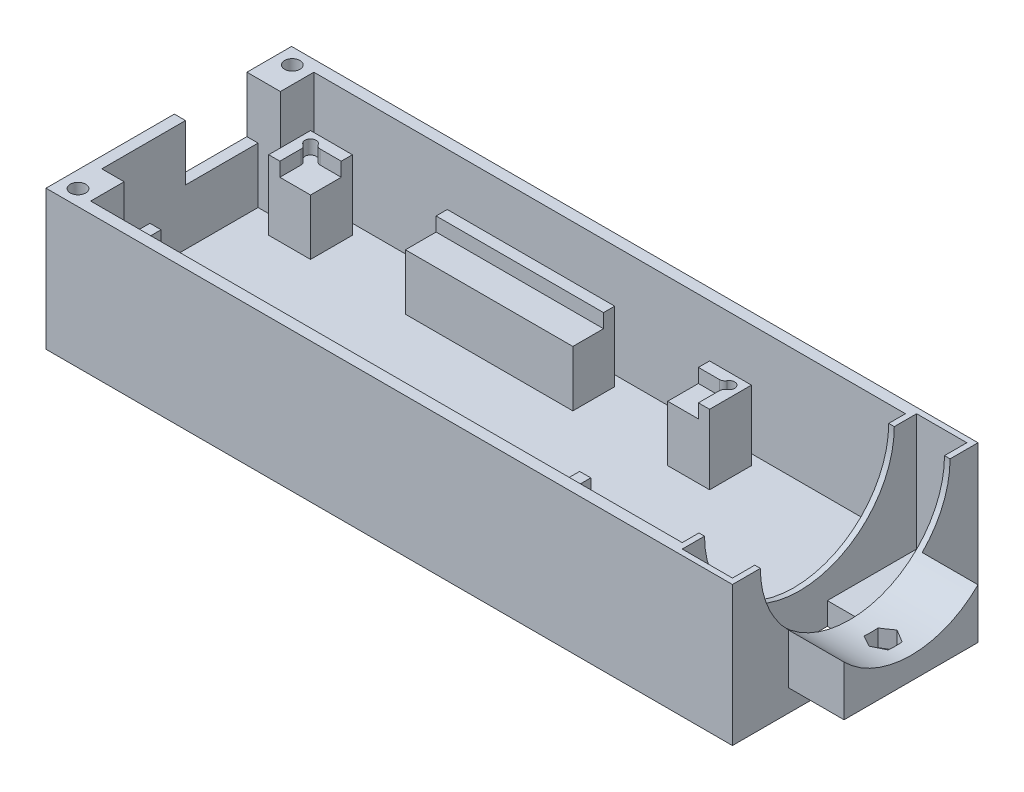
SolidWorks part; units mm, degrees
ref_plane "Front Plane" through (0, 0, 0) normal (0, 0, 1) x (1, 0, 0)
ref_plane "Top Plane" through (0, 0, 0) normal (0, 1, 0) x (1, 0, 0)
ref_plane "Right Plane" through (0, 0, 0) normal (1, 0, 0) x (0, 0, -1)
sketch "Sketch2" plane through (0, 0, 0) normal (0, 1, 0) x (1, 0, 0)
  line L4 (451.485, -2.54) -> (374.015, -2.54)
  line L5 (451.485, -2.54) -> (451.485, 74.93)
  line L6 (451.485, 74.93) -> (374.015, 74.93)
  line L7 (374.015, -2.54) -> (374.015, 74.93)
  line L8 (469.9, -19.685) -> (-50.8, -19.685)
  line L9 (469.9, -19.685) -> (469.9, 92.075)
  line L10 (469.9, 92.075) -> (-50.8, 92.075)
  line L11 (-50.8, -19.685) -> (-50.8, 92.075)
  line L12 (449.58, -0.635) -> (317.5, -0.635)
  line L13 (449.58, -0.635) -> (449.58, 89.789)
  line L14 (449.58, 89.789) -> (317.5, 89.789)
  line L15 (317.5, -0.635) -> (317.5, 89.789)
  line L16 (445.77, 3.175) -> (326.263, 3.175)
  line L17 (445.77, 3.175) -> (445.77, 85.979)
  line L18 (445.77, 85.979) -> (326.263, 85.979)
  line L19 (326.263, 3.175) -> (326.263, 85.979)
  line L20 (326.263, 48.895) -> (313.944, 48.895)
  line L21 (326.263, 48.895) -> (326.263, 77.089)
  line L22 (326.263, 77.089) -> (313.944, 77.089)
  line L23 (313.944, 48.895) -> (313.944, 77.089)
  line L24 (313.944, 68.453) -> (307.34, 68.453)
  line L25 (313.944, 68.453) -> (313.944, 77.089)
  line L26 (313.944, 77.089) -> (307.34, 77.089)
  line L27 (307.34, 68.453) -> (307.34, 77.089)
  line L28 (209.55, 92.075) -> (209.55, -19.685)
  line L33 (209.55, 48.895) -> (184.15, 61.595)
  line L34 (184.15, 61.595) -> (184.15, 10.795)
  line L35 (184.15, 10.795) -> (209.55, 23.495)
  circle A0 centre (412.75, 36.195) radius 20.32
  circle A1 centre (412.75, 36.195) radius 29.21
  point P34 (0, 0)
  dimension "D1" = 40.64
  dimension "D2" = 58.42
  dimension "D3" = 82.804
  dimension "D4" = 90.424
  dimension "D5" = 132.08
  dimension "D6" = 119.507
  dimension "D7" = 3.81
  dimension "D8" = 3.81
  dimension "D9" = 28.194
  dimension "D10" = 8.636
  dimension "D11" = 12.319
  dimension "D12" = 520.7
  dimension "D13" = 33.02
  dimension "D14" = 33.02
  dimension "D15" = 111.76
  dimension "D16" = 77.47
  dimension "D17" = 57.15
  dimension "D18" = 38.735
  dimension "D19" = 77.47
  dimension "D20" = 38.735
  dimension "D21" = 50.8
  dimension "D22" = 8.89
  dimension "D23" = 55.88
  dimension "D24" = 12.7
  dimension "D25" = 25.4
  dimension "D26" = 12.7
  dimension "D27" = 25.4
sketch "Sketch3" plane through (0, 0, 0) normal (0, 1, 0) x (1, 0, 0)
  line L1 (-50.8, 92.075) -> (469.9, 92.075)
  line L2 (-50.8, 92.075) -> (-50.8, -19.685)
  line L3 (-50.8, -19.685) -> (469.9, -19.685)
  line L4 (469.9, 92.075) -> (469.9, -19.685)
extrude "Boss-Extrude1" add sketch "Sketch3" along normal blind 63.5
extrude "Cut-Extrude1" cut sketch "Sketch2" along normal blind 111.76 from offset 6.35 contours L6 L7 L4 L5
sketch "Sketch4" plane through (0, 0, 19.685) normal (0, 0, 1) x (1, 0, 0)
  line L0 (469.9, 0) -> (254, 0)
  line L1 (-50.8, 0) -> (469.9, 0) construction
  line L2 (469.9, 12.7) -> (330.2, 12.7)
  line L4 (469.9, 63.5) -> (469.9, 0) construction
  line L5 (330.2, 12.7) -> (279.4, 63.5)
  line L7 (469.9, 12.7) -> (469.9, 63.5)
  line L8 (279.4, 63.5) -> (469.9, 63.5)
  circle A0 centre (330.2, 63.5) radius 50.8
  line M3 (469.9, 0) -> (469.9, 63.5)
  line M4 (469.9, 63.5) -> (-50.8, 63.5)
  dimension "D1" = 215.9
  dimension "D2" = 139.7
  dimension "D3" = 12.7
  dimension "D4" = 135
  dimension "D5" = 50.8
extrude "Cut-Extrude2" cut sketch "Sketch4" against normal blind 156.718 contours L8 L5 L7 M4 | L5 L2 M3 M4 | L8 A0 L5 M4 | L5 A0 | A0 region at (419.355, 36.5649, 19.685) region at (300.5338, 33.8338, 19.685) region at (336.7868, 43.7396, 19.685) region at (330.2, 85.0602, 19.685)
sketch "Sketch5" plane through (0, 0, 0) normal (1, 0, 0) x (0, 0, -1)
  line L1 (92.075, 63.5) -> (-19.685, 63.5) construction
  circle A0 centre (36.195, 63.5) radius 43.18
  dimension "D1" = 86.36
extrude "Cut-Extrude3" cut sketch "Sketch5" along normal blind 355.6 contours A0
sketch "Sketch6" plane through (0, 63.5, 0) normal (0, 1, 0) x (1, 0, 0)
  line L0 (469.9, -19.685) -> (-50.8, -19.685) construction
  line L1 (-45.72, -14.605) -> (233.68, -14.605)
  line L2 (-45.72, -14.605) -> (-45.72, 86.995)
  line L3 (-45.72, 86.995) -> (233.68, 86.995)
  line L4 (233.68, -14.605) -> (233.68, 86.995)
  line L5 (-50.8, -19.685) -> (-50.8, 92.075) construction
  dimension "D1" = 101.6
  dimension "D2" = 5.08
  dimension "D3" = 5.08
  dimension "D4" = 279.4
extrude "Cut-Extrude4" cut sketch "Sketch6" against normal blind 50.8
sketch "Sketch7" plane through (0, 63.5, 0) normal (0, 1, 0) x (1, 0, 0)
  line L0 (245.1614, -13.805) -> (237.4386, -13.805)
  line L1 (231.3, 36.195) -> (251.3, 36.195)
  line L2 (241.3, 36.195) -> (241.3, -13.805)
  line L3 (-45.72, 36.195) -> (169.3056, 36.195)
  line L4 (-45.72, 86.995) -> (-45.72, -14.605) construction
  arc A0 (237.4386, -13.805) -> (231.3, 36.195) centre (438, 36.195) cw
  arc A1 (245.1614, -13.805) -> (251.3, 36.195) centre (44.6, 36.195) ccw
  dimension "D1" = 287.02
revolve "Cut-Revolve1" cut sketch "Sketch7" angle 360 about L3 region at (243.6576, 63.5, 10.203) region at (245.6519, 63.5, -16.5343)
sketch "Sketch8" plane through (0, 0, 0) normal (0, -1, 0) x (1, 0, 0)
  line L0 (261.62, 19.685) -> (261.62, -5.715)
  line L1 (469.9, 19.685) -> (-50.8, 19.685) construction
  line L2 (469.9, -92.075) -> (-50.8, -92.075) construction
  line L3 (261.62, -66.675) -> (287.02, -66.675)
  line L4 (287.02, -66.675) -> (287.02, -5.715)
  line L5 (287.02, -5.715) -> (261.62, -5.715)
  line L6 (-50.8, 19.685) -> (-50.8, -92.075) construction
  line L7 (261.62, 19.685) -> (609.548, 88.4252)
  line L8 (609.548, 88.4252) -> (609.548, -173.8625)
  line L9 (609.548, -173.8625) -> (261.62, -92.075)
  line L10 (261.62, -66.675) -> (261.62, -92.075)
  dimension "D1" = 312.42
  dimension "D2" = 25.4
  dimension "D3" = 25.4
  dimension "D4" = 25.4
extrude "Cut-Extrude5" cut sketch "Sketch8" against normal blind 174.244 contours L9 L10 L3 L4 L5 L0 L7 L8
sketch "Sketch9" plane through (0, 0, 0) normal (0, -1, 0) x (1, 0, 0)
  line L1 (287.02, -5.715) -> (261.62, -5.715)
  line L2 (287.02, -5.715) -> (287.02, -66.675)
  line L3 (287.02, -66.675) -> (261.62, -66.675)
  line L4 (261.62, -5.715) -> (261.62, -66.675)
extrude "Cut-Extrude6" cut sketch "Sketch9" against normal blind 10.16
sketch "Sketch11" plane through (0, 63.5, 0) normal (0, 1, 0) x (1, 0, 0)
  line L1 (-50.8, 92.075) -> (-35.56, 92.075)
  line L2 (-50.8, 92.075) -> (-50.8, 71.755)
  line L3 (-50.8, 71.755) -> (-35.56, 71.755)
  line L4 (-35.56, 92.075) -> (-35.56, 71.755)
  line L5 (-50.8, -19.685) -> (-35.56, -19.685)
  line L6 (-50.8, -19.685) -> (-50.8, 0.635)
  line L7 (-50.8, 0.635) -> (-35.56, 0.635)
  line L8 (-35.56, -19.685) -> (-35.56, 0.635)
  dimension "D1" = 15.24
  dimension "D2" = 20.32
  dimension "D3" = 20.32
  dimension "D4" = 15.24
extrude "Boss-Extrude2" add sketch "Sketch11" against normal up to next
sketch "Sketch10" plane through (0, 0, 0) normal (0, -1, 0) x (1, 0, 0)
  line L0 (-50.8, -92.075) -> (-50.8, 19.685) construction
  line L1 (261.62, -92.075) -> (-50.8, -92.075) construction
  line L2 (252.3, -92.075) -> (241.3, -92.075)
  line L3 (246.8, -91.3139) -> (252.3, -88.1384)
  line L4 (252.3, -88.1384) -> (252.3, -81.7876)
  line L5 (252.3, -81.7876) -> (246.8, -78.6121)
  line L6 (246.8, -78.6121) -> (241.3, -81.7876)
  line L7 (241.3, -81.7876) -> (241.3, -88.1384)
  line L8 (241.3, -88.1384) -> (246.8, -91.3139)
  line L9 (246.8, -84.963) -> (-43.346, -84.963)
  line L10 (257.359, -36.195) -> (204.1834, -36.195)
  line L11 (246.8, 12.573) -> (-43.346, 12.573)
  line L12 (241.3, 15.7484) -> (246.8, 18.9239)
  line L13 (241.3, 9.3976) -> (241.3, 15.7484)
  line L14 (246.8, 6.2221) -> (241.3, 9.3976)
  line L15 (252.3, 9.3976) -> (246.8, 6.2221)
  line L16 (252.3, 15.7484) -> (252.3, 9.3976)
  line L17 (246.8, 18.9239) -> (252.3, 15.7484)
  line L18 (252.3, 19.685) -> (241.3, 19.685)
  circle A0 centre (246.8, -84.963) radius 5.5 construction
  circle A1 centre (246.8, -84.963) radius 3.5
  circle A2 centre (-43.346, -84.963) radius 3.5
  circle A3 centre (246.8, 12.573) radius 5.5 construction
  circle A4 centre (-43.346, 12.573) radius 3.5
  circle A5 centre (246.8, 12.573) radius 3.5
  circle A6 centre (-43.346, 12.573) radius 5.5
  circle A7 centre (-43.346, -84.963) radius 5.5
  point P0 (-43.346, -84.963)
  dimension "D5" = 7
  dimension "D6" = 11
  dimension "D7" = 11
  dimension "D1" = 7.454
  dimension "D2" = 7.112
  dimension "D3" = 11
  dimension "D4" = 7.112
extrude "Cut-Extrude7" cut sketch "Sketch10" against normal blind 76.2 contours A4 | A2
extrude "Cut-Extrude8" cut sketch "Sketch10<3>" against normal blind 45.72 contours A6 | A7
sketch "Sketch10<3>" plane through (0, 0, 0) normal (0, -1, 0) x (1, 0, 0) same geometry as "Sketch10"
sketch "Sketch13" plane through (0, 10.16, 0) normal (0, -1, 0) x (1, 0, 0)
  line L0 (261.62, -5.715) -> (261.62, -66.675) construction
  line L1 (252.3, -92.075) -> (241.3, -92.075) construction
  line L3 (268.82, -39.3704) -> (274.32, -42.5459)
  line L4 (274.32, -42.5459) -> (279.82, -39.3704)
  line L5 (279.82, -39.3704) -> (279.82, -33.0196)
  line L6 (279.82, -33.0196) -> (274.32, -29.8441)
  line L7 (274.32, -29.8441) -> (268.82, -33.0196)
  line L8 (268.82, -33.0196) -> (268.82, -39.3704)
  circle A0 centre (274.32, -36.195) radius 3.5
  circle A1 centre (274.32, -36.195) radius 5.5 construction
  dimension "D3" = 7
  dimension "D1" = 12.7
  dimension "D2" = 55.88
  dimension "D4" = 11
extrude "Cut-Extrude9" cut sketch "Sketch13" against normal blind 34.448 contours A0
extrude "Cut-Extrude10" cut sketch "Sketch13<3>" against normal blind 34.448 from offset 2.54 offset against normal yes
sketch "Sketch13<3>" plane through (0, 10.16, 0) normal (0, -1, 0) x (1, 0, 0) same geometry as "Sketch13"
sketch "Sketch14" plane through (0, 12.7, 0) normal (0, 1, 0) x (1, 0, 0)
  line L0 (-50.8, -19.685) -> (261.62, -19.685) construction
  line L1 (-27.28, -4.805) -> (163.22, -4.805)
  line L2 (-27.28, -4.805) -> (-27.28, 77.195)
  line L3 (-27.28, 77.195) -> (163.22, 77.195)
  line L4 (163.22, -4.805) -> (163.22, 77.195)
  line L5 (-27.28, -4.805) -> (163.22, 77.195) construction
  line L6 (-27.28, 77.195) -> (163.22, -4.805) construction
  line L7 (241.3, -13.805) -> (241.3, 86.195) construction
  line L8 (163.22, 51.195) -> (236.22, 51.195)
  line L9 (163.22, 51.195) -> (163.22, 21.195)
  line L10 (163.22, 21.195) -> (236.22, 21.195)
  line L11 (236.22, 51.195) -> (236.22, 21.195)
  line L12 (67.97, 36.195) -> (-59.3898, 36.195)
  line L13 (-32.36, 82.275) -> (-13.31, 82.275)
  line L14 (-32.36, 82.275) -> (-32.36, 63.225)
  line L15 (-32.36, 63.225) -> (-13.31, 63.225)
  line L16 (-13.31, 82.275) -> (-13.31, 63.225)
  line L17 (149.25, 82.275) -> (168.3, 82.275)
  line L18 (149.25, 82.275) -> (149.25, 63.225)
  line L19 (149.25, 63.225) -> (168.3, 63.225)
  line L20 (168.3, 82.275) -> (168.3, 63.225)
  line L21 (168.3, -9.885) -> (168.3, 9.165)
  line L22 (149.25, 9.165) -> (168.3, 9.165)
  line L23 (149.25, -9.885) -> (149.25, 9.165)
  line L24 (149.25, -9.885) -> (168.3, -9.885)
  line L25 (-13.31, -9.885) -> (-13.31, 9.165)
  line L26 (-32.36, 9.165) -> (-13.31, 9.165)
  line L27 (-32.36, -9.885) -> (-32.36, 9.165)
  line L28 (-32.36, -9.885) -> (-13.31, -9.885)
  line L30 (163.22, -4.805) -> (37.22, -4.805)
  line L31 (163.22, -4.805) -> (163.22, 77.195)
  line L32 (163.22, 77.195) -> (37.22, 77.195)
  line L33 (37.22, -4.805) -> (37.22, 77.195)
  line L34 (106.07, -9.885) -> (29.87, -9.885)
  line L35 (106.07, -9.885) -> (106.07, 9.165)
  line L36 (106.07, 9.165) -> (29.87, 9.165)
  line L37 (29.87, -9.885) -> (29.87, 9.165)
  line L38 (106.07, 63.225) -> (29.87, 63.225)
  line L39 (106.07, 63.225) -> (106.07, 82.275)
  line L40 (106.07, 82.275) -> (29.87, 82.275)
  line L41 (29.87, 63.225) -> (29.87, 82.275)
  point P0 (67.97, 36.195)
  dimension "D1" = 55.88
  dimension "D2" = 82
  dimension "D3" = 190.5
  dimension "D4" = 73
  dimension "D5" = 26
  dimension "D6" = 26
  dimension "D7" = 5.08
  dimension "D8" = 5.08
  dimension "D9" = 5.08
  dimension "D10" = 19.05
  dimension "D11" = 19.05
  dimension "D12" = 19.05
  dimension "D13" = 5.08
  dimension "D14" = 5.08
  dimension "D15" = 19.05
  dimension "D16" = 126
  dimension "D17" = 64.5
  dimension "D18" = 76.2
  dimension "D19" = 57.15
extrude "Boss-Extrude3" add sketch "Sketch14" along normal blind 25.4 contours L20 L17 L18 L3 L4 L19 | L18 L19 L4 L3 | L14 L15 L16 L13 | L21 L22 L23 L24 | L26 L25 L28 L27 | L40 L41 L38 L39 | L36 L37 L34 L35 region at (149.5194, 12.7, -79.735) region at (156.235, 12.7, -70.21)
extrude "Boss-Extrude4" add sketch "Sketch14<3>" along normal blind 31.75 contours L27 L28 L25 L1 L2 L26 | L16 L13 L14 L15 L2 L3 | L20 L17 L18 L3 L4 L19 | L23 L24 L21 L22 L4 L1 | L37 L34 L35 L30 | L41 L32 L39 L40 region at (-20.295, 12.7, 5.0744) region at (67.97, 12.7, 7.345) region at (-29.82, 12.7, -63.4944) region at (156.235, 12.7, 5.0744) region at (67.97, 12.7, -79.735) region at (149.5194, 12.7, -79.735)
sketch "Sketch14<3>" plane through (0, 12.7, 0) normal (0, 1, 0) x (1, 0, 0) same geometry as "Sketch14"
sketch "Sketch16" plane through (0, 63.5, 0) normal (0, 1, 0) x (1, 0, 0)
  line L0 (-50.8, -19.685) -> (261.62, -19.685) construction
  line L1 (259.08, -17.145) -> (236.22, -17.145)
  line L2 (259.08, -17.145) -> (259.08, 89.535)
  line L3 (259.08, 89.535) -> (236.22, 89.535)
  line L4 (236.22, -17.145) -> (236.22, 89.535)
  line L5 (261.62, 92.075) -> (-50.8, 92.075) construction
  line L6 (261.62, -6.985) -> (261.62, -19.685) construction
  line L7 (233.68, -14.605) -> (233.68, -6.985) construction
  dimension "D1" = 2.54
  dimension "D2" = 2.54
  dimension "D3" = 2.54
  dimension "D4" = 2.54
  dimension "D5" = 22.86
extrude "Cut-Extrude12" cut sketch "Sketch16" against normal blind 53.34
sketch "Sketch17" plane through (0, 10.16, 0) normal (0, 1, 0) x (1, 0, 0)
  line L0 (259.08, -17.145) -> (259.08, 89.535) construction
  line L1 (259.08, 48.895) -> (236.22, 48.895)
  line L2 (259.08, 48.895) -> (259.08, 23.495)
  line L3 (259.08, 23.495) -> (236.22, 23.495)
  line L4 (236.22, 48.895) -> (236.22, 23.495)
  line L5 (259.08, 48.895) -> (236.22, 23.495) construction
  line L6 (259.08, 23.495) -> (236.22, 48.895) construction
  point P0 (247.65, 36.195)
  dimension "D1" = 11.43
  dimension "D2" = 22.86
  dimension "D3" = 25.4
extrude "Cut-Extrude13" cut sketch "Sketch17" against normal blind 52.54
sketch "Sketch18" plane through (-50.8, 0, 0) normal (-1, 0, 0) x (0, 0, 1)
  line L0 (-92.075, 63.5) -> (19.685, 63.5) construction
  line L1 (-71.755, 63.5) -> (-38.735, 63.5)
  line L2 (-71.755, 63.5) -> (-71.755, 38.1)
  line L3 (-71.755, 38.1) -> (-38.735, 38.1)
  line L4 (-38.735, 63.5) -> (-38.735, 38.1)
  line L5 (-71.755, 63.5) -> (-71.755, 12.7) construction
  point P6 (0, 0)
  dimension "D1" = 33.02
  dimension "D2" = 25.4
extrude "Cut-Extrude14" cut sketch "Sketch18" against normal blind 17.018
sketch "Sketch19" plane through (0, 38.1, 0) normal (0, 1, 0) x (1, 0, 0)
  circle A0 centre (-27.28, 77.195) radius 2.54
  circle A1 centre (163.22, 77.195) radius 2.54
  circle A2 centre (163.22, -4.805) radius 2.54
  circle A3 centre (-27.28, -4.805) radius 2.54
  dimension "D1" = 5.08
  dimension "D2" = 5.08
  dimension "D3" = 5.08
  dimension "D4" = 5.08
extrude "Cut-Extrude15" cut sketch "Sketch19" along normal blind 23.876
fillet "Fillet1" radius 2.54 8 edges at (-24.74, 41.275, 4.805) (-27.28, 41.275, 2.265) (163.22, 41.275, 2.265) (160.68, 41.275, 4.805) (160.68, 41.275, -77.195) (163.22, 41.275, -74.655) (-27.28, 41.275, -74.655) (-24.74, 41.275, -77.195)
